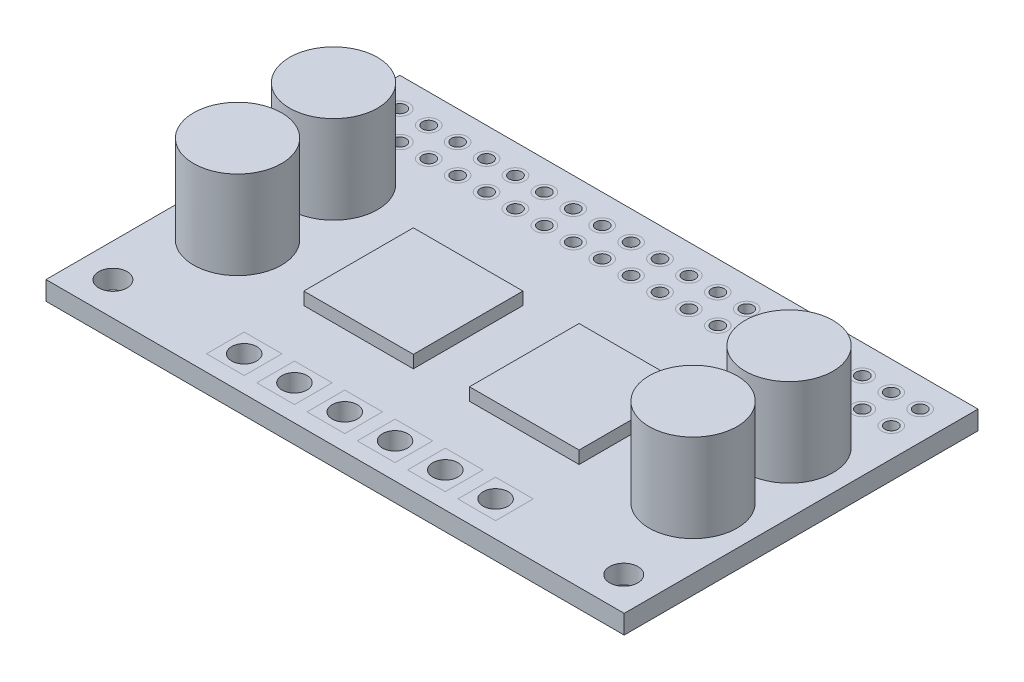
SolidWorks part; units mm, degrees
ref_plane "Front Plane" through (0, 0, 0) normal (0, 0, 1) x (1, 0, 0)
ref_plane "Top Plane" through (0, 0, 0) normal (0, 1, 0) x (1, 0, 0)
ref_plane "Right Plane" through (0, 0, 0) normal (1, 0, 0) x (0, 0, -1)
sketch "Sketch1" plane through (0, 0, 0) normal (0, 1, 0) x (1, 0, 0)
  line L1 (-23, -14.075) -> (23, -14.075)
  line L2 (-23, -14.075) -> (-23, 14.075)
  line L3 (-23, 14.075) -> (23, 14.075)
  line L4 (23, -14.075) -> (23, 14.075)
  line L5 (-23, -14.075) -> (23, 14.075) construction
  line L6 (-23, 14.075) -> (23, -14.075) construction
  line L7 (0, 0) -> (0, 14.075) construction
  circle A0 centre (20.32, -11.43) radius 1.125
  circle A2 centre (-20.32, -11.43) radius 1.125
  point P0 (0, 0)
  dimension "D3" = 2.25
  dimension "D1" = 46
  dimension "D2" = 28.15
  dimension "D4" = 11.43
  dimension "D5" = 20.32
extrude "Boss-Extrude1" add sketch "Sketch1" along normal blind 1.5
sketch "Sketch2" plane through (0, 1.5, 0) normal (0, 1, 0) x (1, 0, 0)
  line L0 (-18.07, -11.43) -> (-18.07, -14.075)
  line L1 (-23, -14.075) -> (23, -14.075) construction
  line L2 (-18.07, -14.075) -> (18.07, -14.075)
  line L3 (18.07, -14.075) -> (18.07, -11.43)
  line L4 (20.32, -9.18) -> (23, -9.18)
  line L5 (23, -14.075) -> (23, 14.075) construction
  line L6 (23, -9.18) -> (23, 14.075)
  line L7 (23, 14.075) -> (-23, 14.075)
  line L8 (-23, 14.075) -> (-23, -9.18)
  line L9 (-23, 14.075) -> (-23, -14.075) construction
  line L10 (-23, -9.18) -> (-20.32, -9.18)
  arc A0 (-18.07, -11.43) -> (-20.32, -9.18) centre (-20.32, -11.43) ccw
  arc A1 (20.32, -9.18) -> (18.07, -11.43) centre (20.32, -11.43) ccw
  dimension "D1" = 4.5
extrude "Boss-Extrude2" [suppressed] add sketch "Sketch2" along normal offset from surface (6.5 mm away) 8 up to face at (20.32, 0, 12.555)
sketch "Sketch3" plane through (0, 1.5, 0) normal (0, 1, 0) x (1, 0, 0)
  line L0 (0, 0) -> (0, 14.075) construction
  line L1 (23, 14.075) -> (-23, 14.075) construction
  circle A0 centre (-18.1212, 3.9224) radius 3.5
  circle A1 centre (-18.1212, -3.7137) radius 3.5
  circle A2 centre (18.1212, -3.7137) radius 3.5
  circle A3 centre (18.1212, 3.9224) radius 3.5
  point P13 (0, 0)
  point P14 (-18.7591, -4.9998)
  point P15 (-18.8298, 2.7064)
  point P16 (-17.9473, 3.9224)
  point P17 (-17.7378, -2.6059)
  point P18 (0, 0)
  point P19 (0, 0)
  point P20 (-18.1212, -3.7137)
  dimension "D1" = 7
extrude "Boss-Extrude3" add sketch "Sketch3" along normal blind 7
sketch "Sketch4" plane through (0, 1.5, 0) normal (0, 1, 0) x (1, 0, 0)
  line L0 (0, 0) -> (0, 14.075) construction
  line L1 (-10.9522, -5.615) -> (-2.2345, -5.615)
  line L2 (-10.9522, -5.615) -> (-10.9522, 3.1028)
  line L3 (-10.9522, 3.1028) -> (-2.2345, 3.1028)
  line L4 (-2.2345, -5.615) -> (-2.2345, 3.1028)
  line L5 (23, 14.075) -> (-23, 14.075) construction
  line L6 (2.2345, -5.615) -> (2.2345, 3.1028)
  line L7 (10.9522, 3.1028) -> (2.2345, 3.1028)
  line L8 (10.9522, -5.615) -> (10.9522, 3.1028)
  line L9 (10.9522, -5.615) -> (2.2345, -5.615)
  point P13 (-2.2345, 3.1028)
extrude "Boss-Extrude4" add sketch "Sketch4" along normal blind 1
sketch "Sketch5" plane through (0, 1.5, 0) normal (0, 1, 0) x (1, 0, 0)
  line L0 (-20.7, 11.775) -> (-20.7, 14.075) construction
  line L1 (23, 14.075) -> (-23, 14.075) construction
  line L2 (-20.7, 11.775) -> (-23, 11.775) construction
  line L3 (-23, 14.075) -> (-23, -14.075) construction
  line L4 (-20.7, 11.775) -> (-18.4, 11.775) construction
  line L5 (-20.7, 11.775) -> (-20.7, 9.475) construction
  line L6 (20.7, 11.775) -> (23, 11.775) construction
  line L7 (23, -14.075) -> (23, 14.075) construction
  circle A0 centre (-20.7, 11.775) radius 0.5
  circle A1 centre (-18.4, 11.775) radius 0.5
  circle A2 centre (-16.1, 11.775) radius 0.5
  circle A3 centre (-13.8, 11.775) radius 0.5
  circle A4 centre (-11.5, 11.775) radius 0.5
  circle A5 centre (-9.2, 11.775) radius 0.5
  circle A6 centre (-6.9, 11.775) radius 0.5
  circle A7 centre (-4.6, 11.775) radius 0.5
  circle A8 centre (-2.3, 11.775) radius 0.5
  circle A9 centre (0, 11.775) radius 0.5
  circle A10 centre (2.3, 11.775) radius 0.5
  circle A11 centre (4.6, 11.775) radius 0.5
  circle A12 centre (6.9, 11.775) radius 0.5
  circle A13 centre (9.2, 11.775) radius 0.5
  circle A14 centre (11.5, 11.775) radius 0.5
  circle A15 centre (13.8, 11.775) radius 0.5
  circle A16 centre (16.1, 11.775) radius 0.5
  circle A17 centre (18.4, 11.775) radius 0.5
  circle A18 centre (20.7, 11.775) radius 0.5
  circle A19 centre (-18.4, 9.475) radius 0.5
  circle A20 centre (-16.1, 9.475) radius 0.5
  circle A21 centre (-13.8, 9.475) radius 0.5
  circle A22 centre (-11.5, 9.475) radius 0.5
  circle A23 centre (-9.2, 9.475) radius 0.5
  circle A24 centre (-6.9, 9.475) radius 0.5
  circle A25 centre (-4.6, 9.475) radius 0.5
  circle A26 centre (-2.3, 9.475) radius 0.5
  circle A27 centre (0, 9.475) radius 0.5
  circle A28 centre (2.3, 9.475) radius 0.5
  circle A29 centre (4.6, 9.475) radius 0.5
  circle A30 centre (6.9, 9.475) radius 0.5
  circle A31 centre (9.2, 9.475) radius 0.5
  circle A32 centre (11.5, 9.475) radius 0.5
  circle A33 centre (13.8, 9.475) radius 0.5
  circle A34 centre (16.1, 9.475) radius 0.5
  circle A35 centre (18.4, 9.475) radius 0.5
  circle A36 centre (20.7, 9.475) radius 0.5
  circle A37 centre (-20.7, 9.475) radius 0.5
  point P2 (19.6979, 10.7729)
  point P83 (0, 0)
  dimension "D1" = 1
  dimension "D2" = 19
  dimension "D3" = 2
extrude "Cut-Extrude1" cut sketch "Sketch5" against normal through all and the other way through all
sketch "Sketch6" plane through (0, 1.5, 0) normal (0, 1, 0) x (1, 0, 0)
  line L0 (-2, -11.3062) -> (2, -11.3062) construction
  circle A0 centre (-10, -11.3062) radius 1
  circle A1 centre (-6, -11.3062) radius 1
  circle A2 centre (-2, -11.3062) radius 1
  circle A3 centre (2, -11.3062) radius 1
  circle A4 centre (6, -11.3062) radius 1
  circle A5 centre (10, -11.3062) radius 1
  point P2 (0, -11.3062)
  point P13 (1.5, -12.0083)
  point P14 (10, -11.3062)
  point P17 (1.889, -10.6609)
  point P18 (7.3309, -18.5672)
  dimension "D1" = 2
  dimension "D3" = 4
  dimension "D2" = 6
extrude "Cut-Extrude2" cut sketch "Sketch6" against normal through all
sketch "Sketch7" plane through (0, 1.5, 0) normal (0, 1, 0) x (1, 0, 0)
  line L0 (-7.5, -12.8062) -> (-4.5, -12.8062)
  line L1 (-11.5, -12.8062) -> (-8.5, -12.8062)
  line L2 (-11.5, -12.8062) -> (-11.5, -9.8062)
  line L3 (-11.5, -9.8062) -> (-8.5, -9.8062)
  line L4 (-8.5, -12.8062) -> (-8.5, -9.8062)
  line L5 (-11.5, -12.8062) -> (-8.5, -9.8062) construction
  line L6 (-11.5, -9.8062) -> (-8.5, -12.8062) construction
  line L7 (-7.5, -9.8062) -> (-4.5, -9.8062)
  line L8 (-4.5, -12.8062) -> (-4.5, -9.8062)
  line L9 (-7.5, -12.8062) -> (-7.5, -9.8062)
  line L10 (-3.5, -12.8062) -> (-0.5, -12.8062)
  line L11 (-3.5, -9.8062) -> (-0.5, -9.8062)
  line L12 (-0.5, -12.8062) -> (-0.5, -9.8062)
  line L13 (-3.5, -12.8062) -> (-3.5, -9.8062)
  line L14 (0.5, -12.8062) -> (3.5, -12.8062)
  line L15 (0.5, -9.8062) -> (3.5, -9.8062)
  line L16 (3.5, -12.8062) -> (3.5, -9.8062)
  line L17 (0.5, -12.8062) -> (0.5, -9.8062)
  line L18 (4.5, -12.8062) -> (7.5, -12.8062)
  line L19 (4.5, -9.8062) -> (7.5, -9.8062)
  line L20 (7.5, -12.8062) -> (7.5, -9.8062)
  line L21 (4.5, -12.8062) -> (4.5, -9.8062)
  line L22 (8.5, -12.8062) -> (11.5, -12.8062)
  line L23 (8.5, -9.8062) -> (11.5, -9.8062)
  line L24 (11.5, -12.8062) -> (11.5, -9.8062)
  line L25 (8.5, -12.8062) -> (8.5, -9.8062)
  line L26 (8.5, -9.8062) -> (11.5, -12.8062) construction
  circle A6 centre (-18.4, 11.775) radius 0.75
  circle A7 centre (-20.7, 11.775) radius 0.75
  circle A8 centre (-20.7, 11.775) radius 0.75
  circle A9 centre (-16.1, 11.775) radius 0.75
  circle A10 centre (-13.8, 11.775) radius 0.75
  circle A11 centre (-11.5, 11.775) radius 0.75
  circle A12 centre (-9.2, 11.775) radius 0.75
  circle A13 centre (-6.9, 11.775) radius 0.75
  circle A14 centre (-4.6, 11.775) radius 0.75
  circle A15 centre (-2.3, 11.775) radius 0.75
  circle A16 centre (0, 11.775) radius 0.75
  circle A17 centre (2.3, 11.775) radius 0.75
  circle A18 centre (4.6, 11.775) radius 0.75
  circle A19 centre (6.9, 11.775) radius 0.75
  circle A20 centre (9.2, 11.775) radius 0.75
  circle A21 centre (11.5, 11.775) radius 0.75
  circle A22 centre (13.8, 11.775) radius 0.75
  circle A23 centre (16.1, 11.775) radius 0.75
  circle A24 centre (18.4, 11.775) radius 0.75
  circle A25 centre (20.7, 11.775) radius 0.75
  circle A26 centre (-18.4, 9.475) radius 0.75
  circle A27 centre (-16.1, 9.475) radius 0.75
  circle A28 centre (-13.8, 9.475) radius 0.75
  circle A29 centre (-11.5, 9.475) radius 0.75
  circle A30 centre (-9.2, 9.475) radius 0.75
  circle A31 centre (-6.9, 9.475) radius 0.75
  circle A32 centre (-4.6, 9.475) radius 0.75
  circle A33 centre (-2.3, 9.475) radius 0.75
  circle A34 centre (0, 9.475) radius 0.75
  circle A35 centre (2.3, 9.475) radius 0.75
  circle A36 centre (4.6, 9.475) radius 0.75
  circle A37 centre (6.9, 9.475) radius 0.75
  circle A38 centre (9.2, 9.475) radius 0.75
  circle A39 centre (11.5, 9.475) radius 0.75
  circle A40 centre (13.8, 9.475) radius 0.75
  circle A41 centre (16.1, 9.475) radius 0.75
  circle A42 centre (18.4, 9.475) radius 0.75
  circle A43 centre (20.7, 9.475) radius 0.75
  circle A44 centre (-20.7, 9.475) radius 0.75
  circle A47 centre (10, -11.3062) radius 1 construction
  point P0 (-10, -11.3062)
  point P84 (10, -11.3062)
  dimension "D4" = 3
  dimension "D1" = 0.25
  dimension "D2" = 19
  dimension "D3" = 2
  dimension "D5" = 6
split line "Split Line1"
